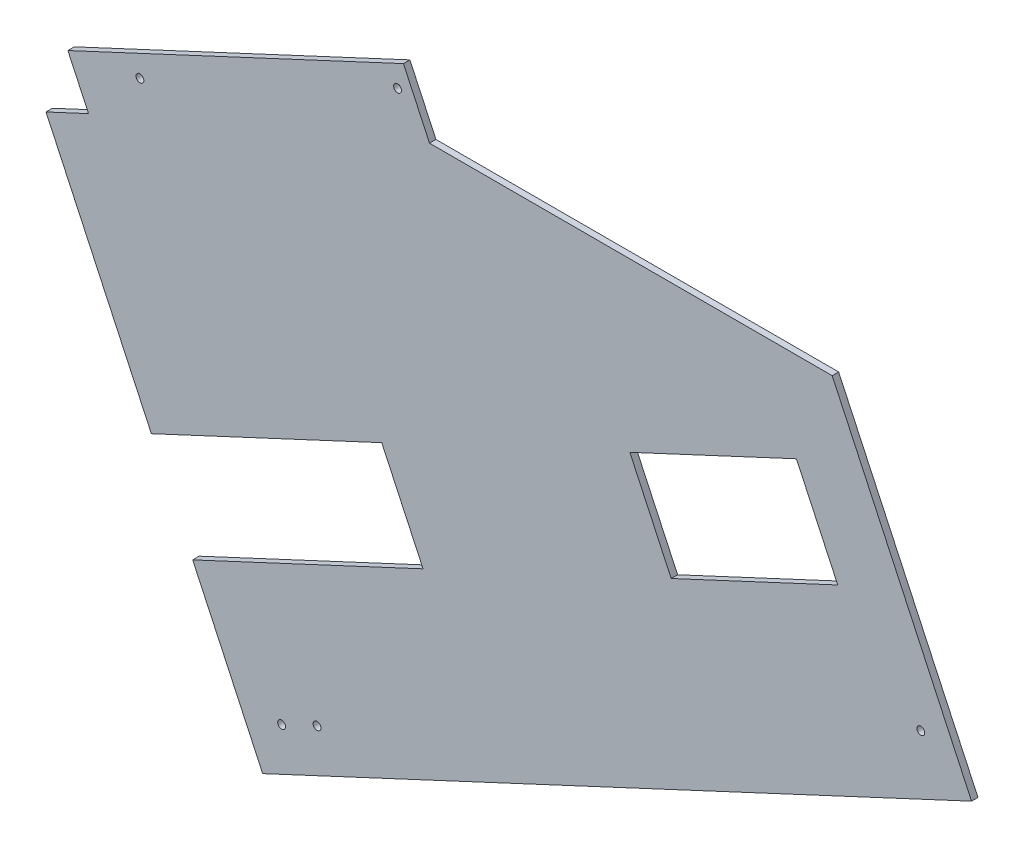
SolidWorks part; units mm, degrees
material "Balsa"
ref_plane "Front Plane" through (0, 0, 0) normal (0, 0, 1) x (1, 0, 0)
ref_plane "Top Plane" through (0, 0, 0) normal (0, 1, 0) x (1, 0, 0)
ref_plane "Right Plane" through (0, 0, 0) normal (1, 0, 0) x (0, 0, -1)
sketch "Sketch1" plane through (0, 0, 0) normal (0, 0, 1) x (1, 0, 0)
  line L0 (327.4362, 0.0035) -> (121.4984, 0.0035)
  line L1 (121.4984, 0.0035) -> (108.169, 28.5884)
  line L2 (108.169, 28.5884) -> (-63.4467, -51.4373)
  line L3 (-63.4467, -51.4373) -> (57.9293, -311.7289) construction
  line L4 (57.9293, -311.7289) -> (398.701, -152.8244)
  line L5 (271.5352, 119.8836) -> (277.3251, 107.4672) construction
  line L6 (190.5834, 136.311) -> (-12.0446, 41.824) construction
  line L7 (-63.4467, -51.4373) -> (255.5737, 97.3243) construction
  line L8 (398.701, -152.8244) -> (327.4362, 0.0035)
  line L9 (57.9293, -311.7289) -> (36.1779, -321.8717)
  line L10 (36.1779, -321.8717) -> (-74.6326, -84.2378)
  line L11 (50.7481, 0) -> (323.7481, 0) construction
  line L12 (-74.6326, -84.2378) -> (-52.8812, -74.095)
  line L13 (-90.9879, -49.1637) -> (-85.1981, -61.5801) construction
  line L14 (-52.8812, -74.095) -> (-63.4467, -51.4373)
  circle A0 centre (162.7613, -40.6644) radius 32.5 construction
  circle A1 centre (336.0773, -108.8767) radius 32.5 construction
  circle A2 centre (90.1802, -40.6644) radius 32.5 construction
  circle A3 centre (232.5481, -40.6644) radius 32.5 construction
  circle A4 centre (207.2768, 100.5118) radius 39.5 construction
  arc A5 (-3.3339, 41.4724) -> (-17.3744, 34.9252) centre (-8.0297, 33.2141) ccw construction
  circle A6 centre (304.5287, -40.6644) radius 32.5 construction
  circle A7 centre (254.9584, -108.8767) radius 32.5 construction
  circle A8 centre (179.3206, -108.8767) radius 32.5 construction
  circle A9 centre (101.4264, -108.8767) radius 32.5 construction
  circle A10 centre (270.383, -163.8108) radius 32.5 construction
  circle A11 centre (372.7594, -134.5783) radius 2
  dimension "D2" = 65
  dimension "D3" = 65
  dimension "D5" = 4
  dimension "D1" = 350
  dimension "D4" = 25
  dimension "24.5/2" = 15.8
  dimension "D6" = 27.5
extrude "Boss-Extrude1" add sketch "Sketch1" along normal up to surface (3.3 mm away)
sketch "Sketch2" plane through (0, 0, 3.3) normal (0, 0, 1) x (1, 0, 0)
  circle A0 centre (105.1447, 16.1444) radius 2
  circle A1 centre (-26.5934, -45.2861) radius 2
  circle A2 centre (-26.5934, -45.2861) radius 2 construction
  circle A3 centre (105.1447, 16.1444) radius 2 construction
extrude "Cut-Extrude1" cut sketch "Sketch2" against normal through all
sketch "Sketch3" plane through (0, 0, 3.3) normal (0, 0, 1) x (1, 0, 0)
  line L2 (398.701, -152.8244) -> (36.1779, -321.8717) construction
  line L3 (36.1779, -321.8717) -> (-74.6326, -84.2378) construction
  circle A0 centre (45.8517, -295.2932) radius 2
  circle A1 centre (63.9779, -286.8408) radius 2
  dimension "D1" = 4
  dimension "D2" = 4
  dimension "D3" = 20
  dimension "D5" = 20
  dimension "D6" = 20
  dimension "D4" = 20
extrude "Cut-Extrude2" cut sketch "Sketch3" against normal blind 4
sketch "Sketch4" plane through (0, 0, 3.3) normal (0, 0, 1) x (1, 0, 0)
  line L0 (330.2782, -91.2744) -> (309.1473, -45.959)
  line L1 (309.1473, -45.959) -> (223.9543, -85.6851)
  line L2 (223.9543, -85.6851) -> (245.0853, -131.0005)
  line L3 (245.0853, -131.0005) -> (330.2782, -91.2744)
  line L4 (309.1473, -45.959) -> (223.9543, -85.6851) construction
  line L5 (245.0853, -131.0005) -> (330.2782, -91.2744) construction
  line L6 (330.2782, -91.2744) -> (309.1473, -45.959) construction
  line L7 (118.2022, -190.1671) -> (97.0712, -144.8517)
  line L8 (97.0712, -144.8517) -> (-20.7488, -199.7921)
  line L9 (-20.7488, -199.7921) -> (0.3821, -245.1075)
  line L10 (0.3821, -245.1075) -> (118.2022, -190.1671)
  line L11 (118.2022, -190.1671) -> (0.3821, -245.1075) construction
  line L12 (-20.7488, -199.7921) -> (97.0712, -144.8517) construction
  line L13 (97.0712, -144.8517) -> (118.2022, -190.1671) construction
extrude "Cut-Extrude3" cut sketch "Sketch4" against normal blind 10
